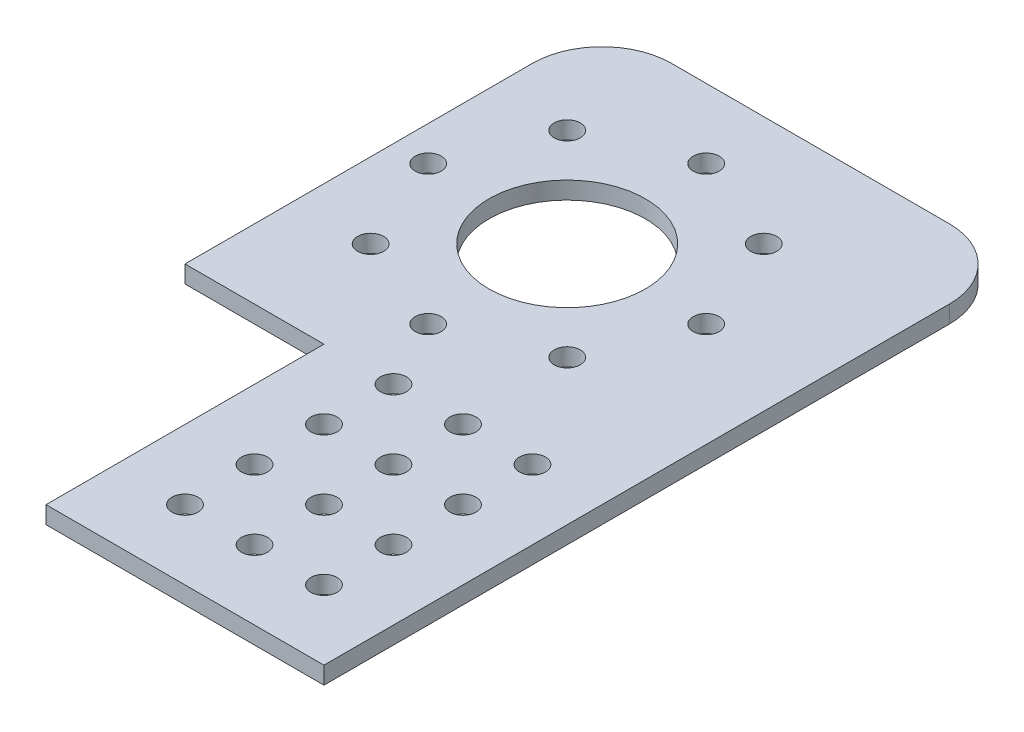
SolidWorks part; units mm, degrees
ref_plane "Front Plane" through (0, 0, 0) normal (0, 0, 1) x (1, 0, 0)
ref_plane "Top Plane" through (0, 0, 0) normal (0, 1, 0) x (1, 0, 0)
ref_plane "Right Plane" through (0, 0, 0) normal (1, 0, 0) x (0, 0, -1)
sketch "Sketch1" plane through (0, 0, 0) normal (0, 1, 0) x (1, 0, 0)
  line L1 (0, 0) -> (50.8, 0)
  line L2 (0, 0) -> (0, 50.8)
  line L3 (-25.4, 127) -> (50.8, 127)
  line L4 (50.8, 0) -> (50.8, 127)
  line L7 (0, 50.8) -> (-25.4, 50.8)
  line L8 (-25.4, 127) -> (-25.4, 50.8)
  circle A0 centre (12.7, 12.7) radius 2.3813
  circle A3 centre (25.4, 12.7) radius 2.3812
  circle A4 centre (38.1, 12.7) radius 2.3812
  circle A5 centre (25.4, 25.4) radius 2.3812
  circle A6 centre (38.1, 25.4) radius 2.3812
  circle A7 centre (25.4, 38.1) radius 2.3813
  circle A8 centre (38.1, 38.1) radius 2.3812
  circle A15 centre (12.7, 25.4) radius 2.3813
  circle A16 centre (12.7, 38.1) radius 2.3813
  circle A26 centre (6.35, 88.9) radius 14.2875
  circle A27 centre (12.7, 50.8) radius 2.3812
  circle A28 centre (25.4, 50.8) radius 2.3812
  circle A29 centre (38.1, 50.8) radius 2.3813
  dimension "D1" = 12.7
  dimension "D3" = 4.7625
  dimension "D4" = 3
  dimension "D11" = 28.575
  dimension "D7" = 127
  dimension "D2" = 12.7
  dimension "D6" = 12.7
  dimension "D8" = 12.7
  dimension "D9" = 12.7
  dimension "D10" = 50.8
  dimension "D12" = 38.1
  dimension "D13" = 31.75
  dimension "D14" = 25.4
  dimension "D5" = 4
extrude "Boss-Extrude1" add sketch "Sketch1" along normal blind 3.175
fillet "Fillet1" radius 12.7 2 edges at (-25.4, 1.5875, -127) (50.8, 1.5875, -127)
sketch "Sketch2" plane through (0, 3.175, 0) normal (0, 1, 0) x (1, 0, 0)
  line L0 (6.35, 88.9) -> (-19.05, 88.9) construction
  line L1 (6.35, 88.9) -> (-11.6105, 106.8605) construction
  circle A0 centre (6.35, 88.9) radius 25.4 construction
  circle A1 centre (-19.05, 88.9) radius 2.3813
  circle A2 centre (-11.6105, 106.8605) radius 2.3812
  circle A3 centre (6.35, 114.3) radius 2.3812
  circle A4 centre (24.3105, 106.8605) radius 2.3812
  circle A5 centre (31.75, 88.9) radius 2.3812
  circle A6 centre (24.3105, 70.9395) radius 2.3812
  circle A7 centre (6.35, 63.5) radius 2.3812
  circle A8 centre (-11.6105, 70.9395) radius 2.3812
  point P5 (6.35, 114.3)
  dimension "D1" = 50.8
  dimension "D2" = 4.7625
  dimension "D4" = 45
  dimension "D3" = 8
extrude "Cut-Extrude1" cut sketch "Sketch2" against normal through all
